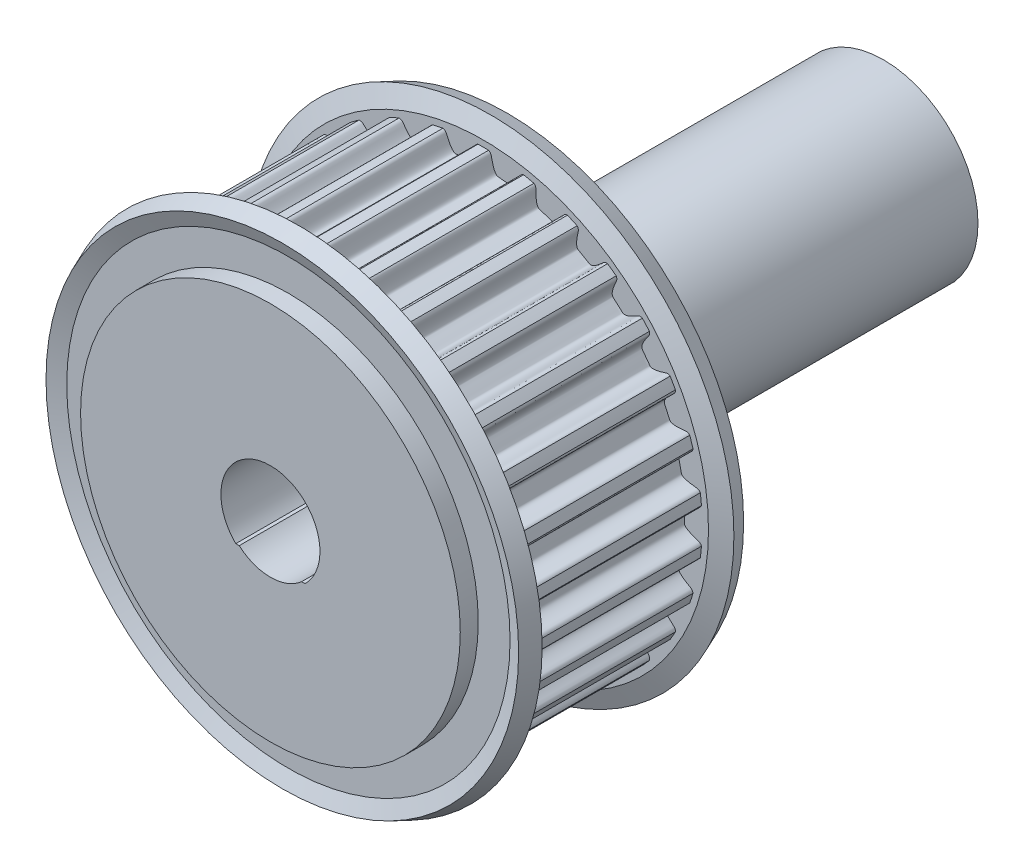
SolidWorks part; units mm, degrees
ref_plane "前视基准面" through (0, 0, 0) normal (0, 0, 1) x (1, 0, 0)
ref_plane "上视基准面" through (0, 0, 0) normal (0, 1, 0) x (1, 0, 0)
ref_plane "右视基准面" through (0, 0, 0) normal (1, 0, 0) x (0, 0, -1)
other "Configuration Table"
ref_axis "基准轴1" through (0, 0, 55) along (0, 0, -1)
sketch "SketchRevolveGearBelt01" plane through (0, 0, 0) normal (1, 0, 0) x (0, 0, -1)
  line L0 (0, 0) -> (1, 0) construction
  line L1 (5.274, 0) -> (5.274, 8.0493)
  line L2 (5.274, 8.0493) -> (4.512, 8.0493)
  line L3 (4.512, 8.0493) -> (4.512, 9.3977)
  line L4 (4.512, 9.3977) -> (4.7696, 10.0197)
  line L5 (4.7696, 10.0197) -> (4.0656, 10.3113)
  line L6 (4.0656, 10.3113) -> (3.75, 9.5493)
  line L7 (3.75, 9.5493) -> (3.75, 9.2805)
  line L8 (3.75, 9.2805) -> (-3.75, 9.2805)
  line L9 (-3.75, 9.2805) -> (-3.75, 9.5493)
  line L10 (-3.75, 9.5493) -> (-4.0656, 10.3113)
  line L11 (-4.0656, 10.3113) -> (-4.7696, 10.0197)
  line L12 (-4.7696, 10.0197) -> (-4.512, 9.3977)
  line L13 (-4.512, 9.3977) -> (-4.512, 8.0493)
  line L14 (-4.512, 8.0493) -> (-5.274, 8.0493)
  line L15 (-5.274, 8.0493) -> (-5.274, 0)
  line L16 (-5.274, 0) -> (5.274, 0)
  dimension "GearBeltFlange1OutsideLength" = 1.3484
  dimension "GearBeltFlange1X" = 0.2576
  dimension "GearBeltFlange1Y" = 0.622
  dimension "GearBeltFlangeThickness" = 0.762
  dimension "GearBeltFlangeInside" = 0.2688
  dimension "GearBeltOutsideDiameter" = 9.2805
  dimension "GearBeltFlange2X" = 0.2576
revolve "Gates_PowerGrip_GT_2mm, 6mm Belt Width" add sketch "SketchRevolveGearBelt01" angle 360 about L0
sketch "SketchToothGearBelt01" plane through (0, 0, 0) normal (0, 0, 1) x (1, 0, 0)
  arc A0 (9.2595, 0.8121) -> (9.2595, -0.8121) centre (0, 0) cw
  spline S0 degree 3 poles (9.2595, -0.8121) (9.2599, -0.7989) (9.2585, -0.7791) (9.2529, -0.7533) (9.2468, -0.7345) (9.2388, -0.7164) (9.2291, -0.6991) (9.2177, -0.6829) (9.2048, -0.6679) (9.1905, -0.6543) (9.1749, -0.6421) (9.1582, -0.6315) (9.1405, -0.6226) (9.0968, -0.6066) (9.0407, -0.5893) (8.974, -0.5675) (8.9232, -0.5498) (8.8755, -0.5322) (8.8309, -0.5145) (8.7894, -0.4969) (8.7509, -0.4793) (8.7155, -0.4616) (8.6831, -0.444) (8.6538, -0.4264) (8.6276, -0.4087) (8.6044, -0.3911) (8.5843, -0.3734) (8.5673, -0.3558) (8.5533, -0.3381) (8.5423, -0.3203) (8.5345, -0.3025) (8.5296, -0.2846) (8.5275, -0.2503) (8.5312, -0.2) (8.5317, -0.1333) (8.5327, -0.0666) (8.5328, 0) (8.5327, 0.0666) (8.5317, 0.1333) (8.5312, 0.2) (8.5275, 0.2503) (8.5296, 0.2846) (8.5345, 0.3025) (8.5423, 0.3203) (8.5533, 0.3381) (8.5673, 0.3558) (8.5843, 0.3734) (8.6044, 0.3911) (8.6276, 0.4087) (8.6538, 0.4264) (8.6831, 0.444) (8.7155, 0.4616) (8.7509, 0.4793) (8.7894, 0.4969) (8.8309, 0.5145) (8.8755, 0.5322) (8.9232, 0.5498) (8.974, 0.5675) (9.0407, 0.5893) (9.0968, 0.6066) (9.1405, 0.6226) (9.1582, 0.6315) (9.1749, 0.6421) (9.1905, 0.6543) (9.2048, 0.6679) (9.2177, 0.6829) (9.2291, 0.6991) (9.2388, 0.7164) (9.2468, 0.7345) (9.2529, 0.7533) (9.2585, 0.7791) (9.2599, 0.7989) (9.2595, 0.8121) knots 0 0 0 0 0.015924 0.023886 0.031848 0.03981 0.047771 0.055733 0.063695 0.071657 0.079619 0.087581 0.095543 0.103505 0.143783 0.166612 0.188267 0.208755 0.228086 0.24627 0.26332 0.279253 0.294087 0.307847 0.320562 0.332271 0.343022 0.352878 0.361922 0.370259 0.378023 0.385381 0.392526 0.419433 0.446289 0.473144 0.5 0.526856 0.553711 0.580567 0.607474 0.614619 0.621977 0.629741 0.638078 0.647122 0.656978 0.667729 0.679438 0.692153 0.705913 0.720747 0.73668 0.75373 0.771914 0.791245 0.811733 0.833388 0.856217 0.896495 0.904457 0.912419 0.920381 0.928343 0.936305 0.944267 0.952229 0.96019 0.968152 0.976114 0.984076 1 1 1 1
extrude "ToothExtrudeCutGearBelt01" cut sketch "SketchToothGearBelt01" against normal blind 3.75 and the other way blind 3.75
pattern_circular "Tooth Pattern, 30" count 30 every 12 about axis through (0, 0, 55) along (0, 0, -1) of "ToothExtrudeCutGearBelt01"
sketch "BoreRevolveSketch" plane through (0, 0, 0) normal (1, 0, 0) x (0, 0, -1)
  line L0 (0, 0) -> (1, 0) construction
  line L1 (-5.274, 0) -> (5.274, 0)
  line L2 (5.274, 0) -> (5.274, 5)
  line L3 (5.274, 5) -> (-5.274, 5)
  line L4 (-5.274, 5) -> (-5.274, 0)
  dimension "TaperSide1" = 5
  dimension "TaperSide2" = 5
revolve "BoreRevolveCut" cut sketch "BoreRevolveSketch" angle 360 about L0
sketch "AuxiliarySketchGearBelt01" plane through (0, 0, 0) normal (0, 0, 1) x (1, 0, 0)
  circle A0 centre (0, 0) radius 9.5493 construction
  dimension "PitchDiameter" = 19.0986
sketch "草图5" plane through (0, 0, 5.274) normal (0, 0, 1) x (1, 0, 0)
  circle A0 centre (0, 0) radius 5
extrude "凸台-拉伸1" add sketch "草图5" against normal blind 11
sketch "草图6" plane through (0, 0, -5.726) normal (0, 0, -1) x (-1, 0, 0)
  circle A0 centre (0, 0) radius 2
  circle A1 centre (0, 0) radius 4
  dimension "D1" = 4
  dimension "D2" = 2
extrude "凸台-拉伸2" add sketch "草图6" along normal blind 15
sketch "草图7" plane through (0, 0, -20.726) normal (0, 0, -1) x (-1, 0, 0)
  line L0 (0, 0) -> (0, -1.5)
  line L1 (-1000, -1.5) -> (49000, -1.5)
  circle A0 centre (0, 0) radius 2.1
  circle M3 centre (0, 0) radius 2
  dimension "D1" = 1.5
extrude "切除-拉伸4" cut sketch "草图7" against normal through all contours L1 A0 M3 region at (0.7921, 1.885, -20.726)
sketch "草图10" plane through (0, 0, -5.726) normal (0, 0, -1) x (-1, 0, 0)
  line L0 (0, 0) -> (0, -1.5)
  line L1 (-1000.0271, -1.4994) -> (48999.9729, -1.4994)
  circle A0 centre (0, 0) radius 2.1
  arc M2 (-1.3229, -1.5) -> (1.3229, -1.5) centre (0, 0) ccw
  arc M3 (1.3229, -1.5) -> (-1.3229, -1.5) centre (0, 0) ccw
  dimension "D1" = 1.5
extrude "凸台-拉伸4" add sketch "草图10" along normal blind 15 contours L1 M3 M2 region at (0, -1.702, -5.726)
sketch "草图11" plane through (0, 0, -5.726) normal (0, 0, -1) x (-1, 0, 0)
  circle A0 centre (0, 0) radius 2
extrude "切除-拉伸5" cut sketch "草图11" against normal through all
